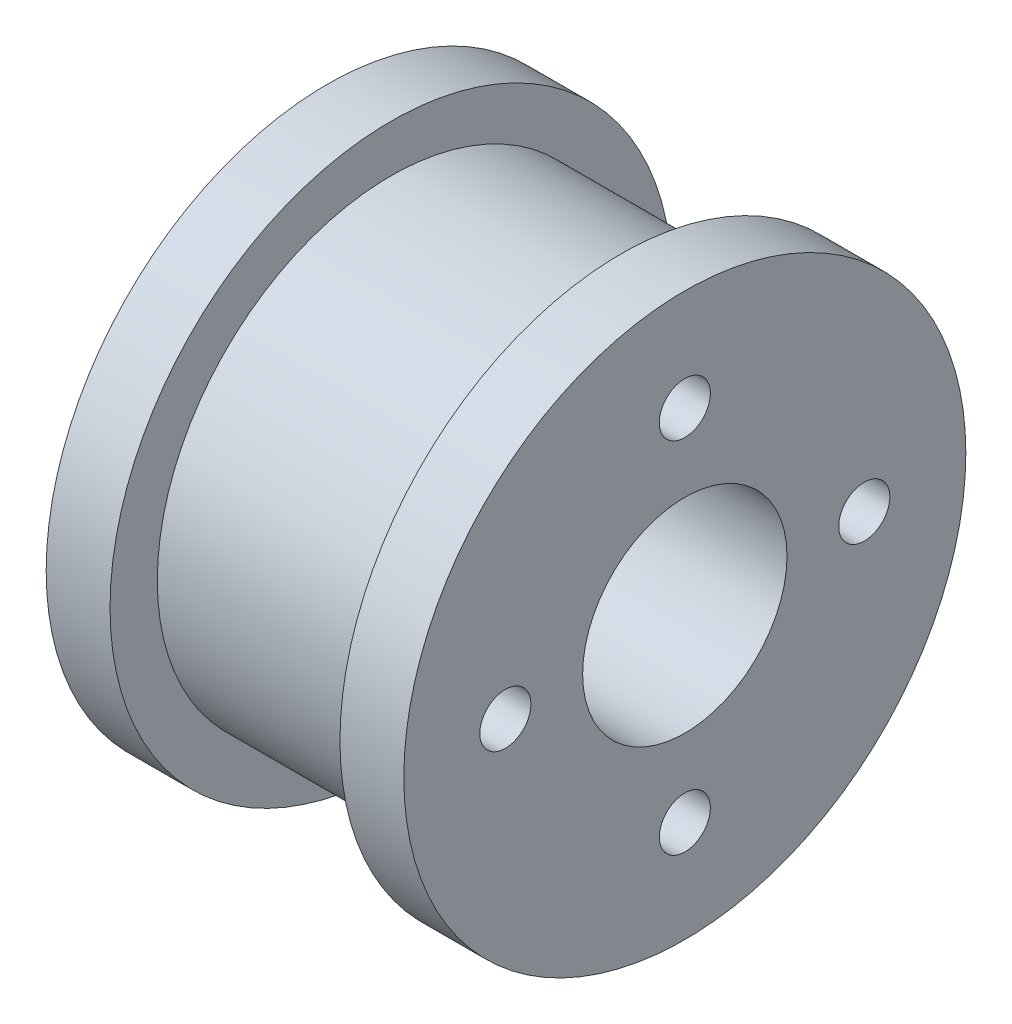
SolidWorks part; units mm, degrees
ref_plane "Front Plane" through (0, 0, 0) normal (0, 0, 1) x (1, 0, 0)
ref_plane "Top Plane" through (0, 0, 0) normal (0, 1, 0) x (1, 0, 0)
ref_plane "Right Plane" through (0, 0, 0) normal (1, 0, 0) x (0, 0, -1)
sketch "Sketch1" plane through (0, 0, 0) normal (1, 0, 0) x (0, 0, -1)
  circle A0 centre (0, 0) radius 11
  dimension "D1" = 22
extrude "Boss-Extrude1" add sketch "Sketch1" along normal blind 2.5
sketch "Sketch2" plane through (2.5, 0, 0) normal (1, 0, 0) x (0, 0, -1)
  circle A0 centre (0, 0) radius 9.15
  dimension "D1" = 18.3
extrude "Boss-Extrude2" add sketch "Sketch2" along normal blind 9
sketch "Sketch3" plane through (11.5, 0, 0) normal (1, 0, 0) x (0, 0, -1)
  circle A0 centre (0, 0) radius 11
extrude "Boss-Extrude3" add sketch "Sketch3" along normal blind 2.5
sketch "Sketch4" plane through (14, 0, 0) normal (1, 0, 0) x (0, 0, -1)
  circle A0 centre (0, 0) radius 4
  dimension "D1" = 8
extrude "Cut-Extrude1" cut sketch "Sketch4" against normal through all
sketch "Sketch5" plane through (14, 0, 0) normal (1, 0, 0) x (0, 0, -1)
  circle A0 centre (0, 0) radius 7.025 construction
  circle A1 centre (0, 0) radius 9.6 construction
  circle A2 centre (0, 0) radius 11 construction
  circle A4 centre (0, 7.025) radius 1
  circle A5 centre (7.025, 0) radius 1
  circle A6 centre (0, -7.025) radius 1
  circle A7 centre (-7.025, 0) radius 1
  dimension "D1" = 1.4
  dimension "D2" = 2.575
  dimension "D3" = 2
  dimension "D4" = 2
  dimension "D5" = 2
  dimension "D6" = 2
extrude "Cut-Extrude2" cut sketch "Sketch5" against normal up to next
